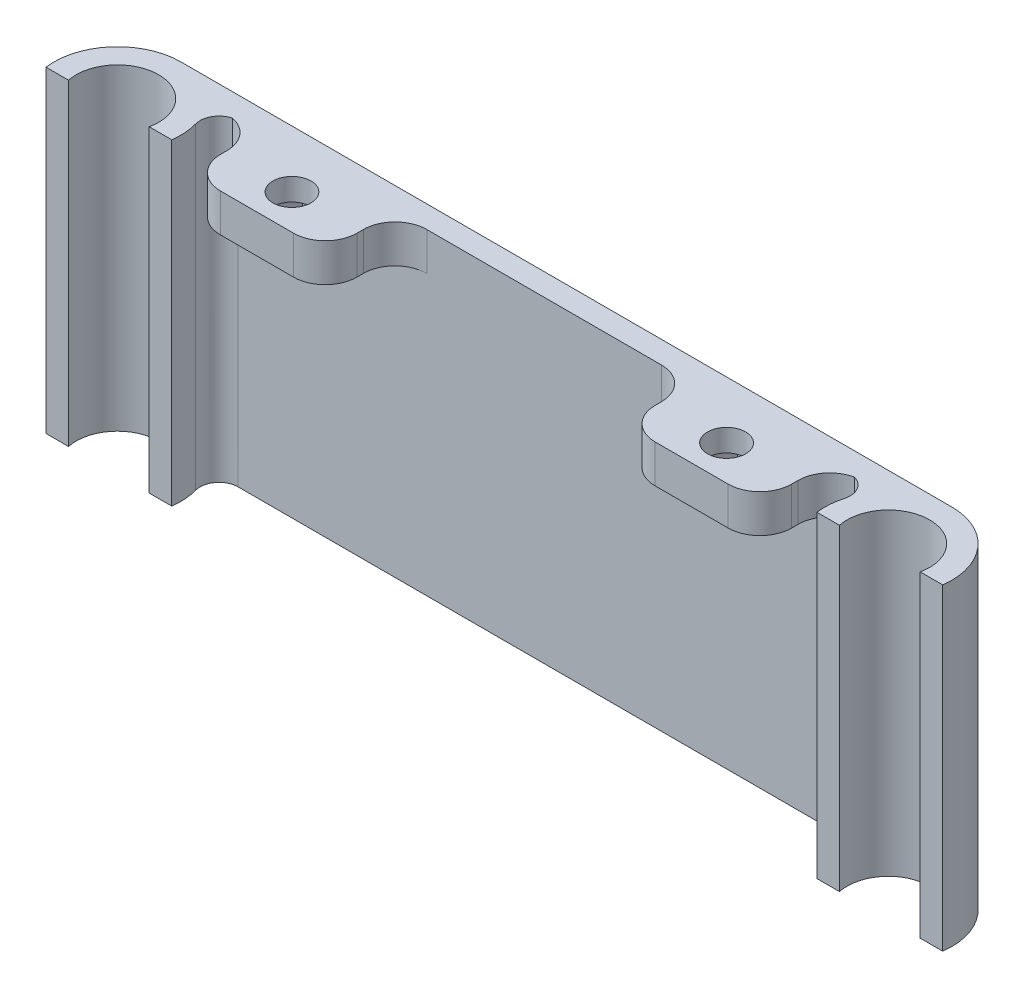
SolidWorks part; units mm, degrees
ref_plane "Front Plane" through (0, 0, 0) normal (0, 0, 1) x (1, 0, 0)
ref_plane "Top Plane" through (0, 0, 0) normal (0, 1, 0) x (1, 0, 0)
ref_plane "Right Plane" through (0, 0, 0) normal (1, 0, 0) x (0, 0, -1)
sketch "Sketch1" plane through (0, 0, 0) normal (0, 1, 0) x (1, 0, 0)
  line L0 (0, 0) -> (-121.5, 0)
  line L1 (-121.5, 10) -> (0, 10)
  line L2 (0, 10) -> (0, 6.5)
  line L3 (0, 6.5) -> (-121.5, 6.5)
  line L4 (-121.5, 0) -> (-121.5, -1.3505)
  line L5 (-121.5, -1.3505) -> (-137.3585, -1.3505)
  line L6 (-137.3585, -1.3505) -> (23.118, -1.3505)
  circle A0 centre (-121.5, 0) radius 6.5
  circle A1 centre (0, 0) radius 6.5
  circle A2 centre (-121.5, 0) radius 10
  circle A3 centre (0, 0) radius 10
extrude "Boss-Extrude2" add sketch "Sketch1" along normal blind 50 contours L6 A3 L2 A1 | L2 A3 L3 | A3 L1 A2 L3 | L3 A3 L0 A1 | L0 A3 L6 A1 | L0 A2 L3 A0 | L3 A2 L6 A0 region at (-114.5212, 0, -3.5511) region at (-6.9788, 0, -3.5511) region at (-8.2111, 0, 0.6768) region at (-60.75, 0, -8.2811) region at (-124.8059, 0, -5.6129) region at (-2.9305, 0, -7.9234) region at (5.6039, 0, -4.7615)
sketch "Sketch2" plane through (0, 50, 0) normal (0, 1, 0) x (1, 0, 0)
  line L0 (-60.75, 6.5) -> (-60.75, -4.5)
  line L1 (-60.75, -4.5) -> (-105.75, -4.5)
  line L2 (-7.5993, 6.5) -> (-113.9007, 6.5) construction
  line L3 (-60.75, -4.5) -> (-15.75, -4.5)
  line L4 (-105.75, -4.5) -> (-105.75, 6.5)
  line L5 (-105.75, 6.5) -> (-15.75, 6.5)
  line L6 (-15.75, 6.5) -> (-15.75, -4.5)
  line L7 (-115, 0) -> (-95, 0)
  line L8 (-6.5, 0) -> (-26.5, 0)
  line L9 (-95, 6.5) -> (-95, -4.5)
  line L10 (-26.5, 6.5) -> (-26.5, -4.5)
  line L11 (-105.75, -4.5) -> (-95, -4.5)
  line L12 (-95, -4.5) -> (-84.25, -4.5)
  line L13 (-26.5, -4.5) -> (-37.25, -4.5)
  line L14 (-37.25, -4.5) -> (-37.25, 6.5)
  line L15 (-37.25, 6.5) -> (-84.25, 6.5)
  line L16 (-84.25, 6.5) -> (-84.25, -4.5)
  line L17 (-131.4084, -1.3505) -> (-107.8559, -1.3505)
  arc A0 (6.3582, -1.3505) -> (-6.3582, -1.3505) centre (0, 0) ccw construction
  circle A3 centre (-95, 1) radius 3
  circle A4 centre (-26.5, 1) radius 3
  circle A5 centre (-121.5, 0) radius 6.5
  circle A6 centre (-121.5, 0) radius 10
  line M14 (-115, 0) -> (-111.5, 0)
  line M16 (-113.9007, 6.5) -> (-7.5993, 6.5)
extrude "Boss-Extrude3" add sketch "Sketch2" against normal blind 6 contours A3 L9 L1 L16 L5 | A3 L7 L4 L1 L9 | A3 L9 L4 L7 M16 | A4 L10 L5 L14 L3 | A4 L8 L6 L5 L10 | A4 L10 L3 L6 L8 | L17 A6 A5 M14 region at (-89.068, 50, -1) region at (-32.432, 50, -1) region at (-101.0512, 50, -3.5003) region at (-20.4488, 50, -3.5003) region at (-100.7706, 50, 2.3825) region at (-20.7294, 50, 2.3825) region at (-113.2889, 50, 0.6768)
sketch "Sketch3" plane through (0, 44, 0) normal (0, -1, 0) x (1, 0, 0)
  line L2 (-111.5916, 1.3505) -> (-115.1418, 1.3505)
  line L3 (-115, 0) -> (-111.5, 0)
  line L4 (-111.5916, 1.3505) -> (-115.1418, 1.3505)
  line L5 (-115, 0) -> (-111.5, 0)
  arc A2 (-115, 0) -> (-115.1418, 1.3505) centre (-121.5, 0) ccw
  arc A3 (-111.5, 0) -> (-111.5916, 1.3505) centre (-121.5, 0) ccw
  arc A4 (-115, 0) -> (-115.1418, 1.3505) centre (-121.5, 0) ccw
  arc A5 (-111.5, 0) -> (-111.5916, 1.3505) centre (-121.5, 0) ccw
  dimension "D1" = 0
extrude "Boss-Extrude4" add sketch "Sketch3" along normal up to surface (44 mm away) up to face at (-60.8146, 0, -3.7377)
fillet "Fillet1" radius 5 8 edges at (-105.75, 47, -6.5) (-84.25, 47, -6.5) (-37.25, 47, -6.5) (-15.75, 47, -6.5) (-15.75, 47, 4.5) (-37.25, 47, 4.5) (-84.25, 47, 4.5) (-105.75, 47, 4.5)
fillet "Fillet2" radius 3 2 edges at (-7.5993, 25, -6.5) (-113.9007, 25, -6.5)
sketch "Sketch5" plane through (0, 44, 0) normal (0, -1, 0) x (1, 0, 0)
  line L1 (-21.8969, -1) -> (-24.1984, 2.9864)
  line L2 (-24.1984, 2.9864) -> (-28.8016, 2.9864)
  line L3 (-28.8016, 2.9864) -> (-31.1031, -1)
  line L4 (-31.1031, -1) -> (-28.8016, -4.9864)
  line L5 (-28.8016, -4.9864) -> (-24.1984, -4.9864)
  line L6 (-24.1984, -4.9864) -> (-21.8969, -1)
  line L7 (-90.4012, -1) -> (-92.7006, 2.9827)
  line L8 (-92.7006, 2.9827) -> (-97.2994, 2.9827)
  line L9 (-97.2994, 2.9827) -> (-99.5988, -1)
  line L10 (-99.5988, -1) -> (-97.2994, -4.9827)
  line L11 (-97.2994, -4.9827) -> (-92.7006, -4.9827)
  line L12 (-92.7006, -4.9827) -> (-90.4012, -1)
  circle A2 centre (-26.5, -1) radius 3.9864 construction
  circle A3 centre (-95, -1) radius 3.9827 construction
extrude "Cut-Extrude3" cut sketch "Sketch5" against normal blind 2.5
sketch "Sketch6" plane through (0, 0, -10) normal (0, 0, -1) x (-1, 0, 0)
  line L0 (0, 25) -> (121.5, 25)
  line L1 (81.9706, 15.178) -> (113.9706, 15.178)
  line L2 (81.9706, 15.178) -> (81.9706, 31.178)
  line L3 (81.9706, 31.178) -> (113.9706, 31.178)
  line L4 (113.9706, 15.178) -> (113.9706, 31.178)
  line L5 (0, 50) -> (0, 0) construction
  line L6 (121.5, 50) -> (121.5, 0) construction
  line L7 (113.9706, 31.178) -> (113.9706, 15.178)
  line L8 (81.9706, 15.178) -> (81.9706, 0.1624)
  circle A0 centre (30.7104, 25) radius 11
  circle A1 centre (59.5022, 25) radius 8
  circle A2 centre (30.7104, 25) radius 16
  circle A3 centre (59.5022, 25) radius 9
  point P14 (30.7104, 25)
